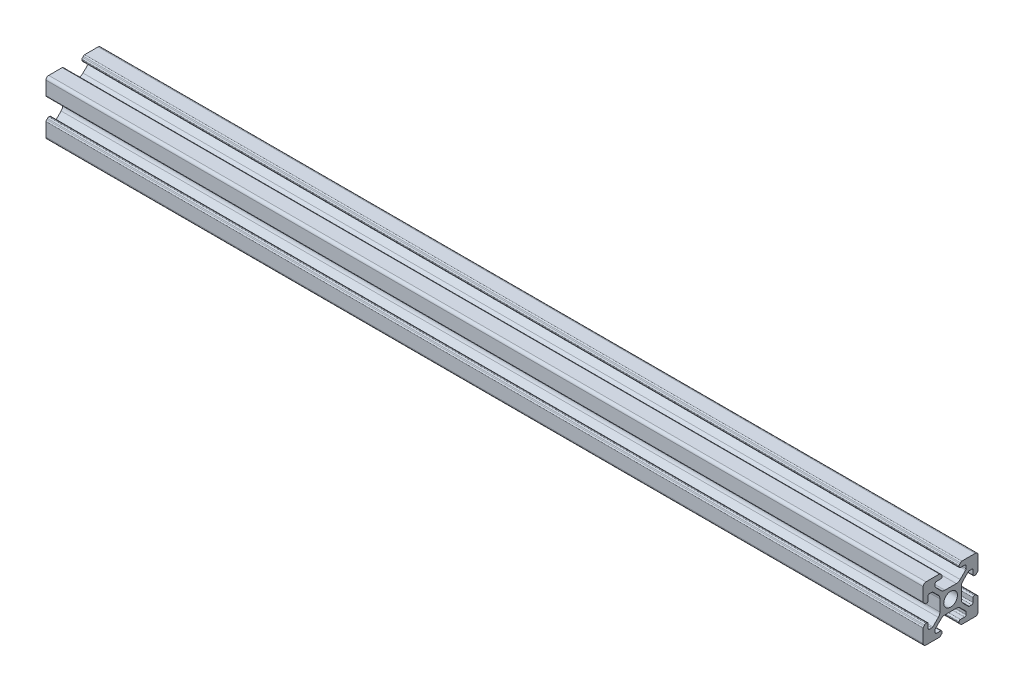
SolidWorks part; units mm, degrees
material "6061 Alloy"
ref_plane "Front Plane" through (0, 0, 0) normal (0, 0, 1) x (1, 0, 0)
ref_plane "Top Plane" through (0, 0, 0) normal (0, 1, 0) x (1, 0, 0)
ref_plane "Right Plane" through (0, 0, 0) normal (1, 0, 0) x (0, 0, -1)
sketch "Sketch1" plane through (0, 0, 0) normal (1, 0, 0) x (0, 0, -1)
  line L0 (10, 10) -> (-10, -10) construction
  line L1 (-10, 10) -> (10, 10)
  line L2 (-10, 10) -> (-10, -10)
  line L3 (-10, -10) -> (10, -10)
  line L4 (10, 10) -> (10, -10)
  dimension "D1" = 20
extrude "Boss-Extrude1" add sketch "Sketch1" along normal blind 320
fillet "Fillet1" radius 1 4 edges at (160, -10, -10) (160, -10, 10) (160, 10, -10) (160, 10, 10)
sketch "Sketch3" plane through (0, 0, 0) normal (-1, 0, 0) x (0, 0, 1)
  line L0 (-3.6, 10) -> (3.6, 10)
  line L1 (-9, 10) -> (9, 10) construction
  line L2 (3.6, 10) -> (3.6, 9.5)
  line L3 (3.6, 9.5) -> (3.1, 9.5)
  line L4 (3.1, 9.5) -> (3.1, 8.2)
  line L5 (3.1, 8.2) -> (5.63, 8.2)
  line L6 (5.63, 8.2) -> (5.63, 6.6199)
  line L7 (5.63, 6.6199) -> (2.9101, 3.9)
  line L8 (2.9101, 3.9) -> (-2.9101, 3.9)
  line L9 (-2.9101, 3.9) -> (-5.63, 6.6199)
  line L10 (-5.63, 6.6199) -> (-5.63, 8.2)
  line L11 (-5.63, 8.2) -> (-3.1, 8.2)
  line L12 (-3.1, 8.2) -> (-3.1, 9.5)
  line L13 (-3.1, 9.5) -> (-3.6, 9.5)
  line L14 (-3.6, 9.5) -> (-3.6, 10)
  line L15 (0, 10) -> (0, 3.9) construction
  line L16 (10, 3.6) -> (10, -3.6)
  line L17 (10, -3.6) -> (9.5, -3.6)
  line L18 (9.5, -3.6) -> (9.5, -3.1)
  line L19 (9.5, -3.1) -> (8.2, -3.1)
  line L20 (8.2, -3.1) -> (8.2, -5.63)
  line L21 (8.2, -5.63) -> (6.6199, -5.63)
  line L22 (6.6199, -5.63) -> (3.9, -2.9101)
  line L23 (3.9, -2.9101) -> (3.9, 2.9101)
  line L24 (3.9, 2.9101) -> (6.6199, 5.63)
  line L25 (6.6199, 5.63) -> (8.2, 5.63)
  line L26 (8.2, 5.63) -> (8.2, 3.1)
  line L27 (8.2, 3.1) -> (9.5, 3.1)
  line L28 (9.5, 3.1) -> (9.5, 3.6)
  line L29 (9.5, 3.6) -> (10, 3.6)
  line L30 (10, 0) -> (3.9, 0) construction
  line L31 (3.6, -10) -> (-3.6, -10)
  line L32 (-3.6, -10) -> (-3.6, -9.5)
  line L33 (-3.6, -9.5) -> (-3.1, -9.5)
  line L34 (-3.1, -9.5) -> (-3.1, -8.2)
  line L35 (-3.1, -8.2) -> (-5.63, -8.2)
  line L36 (-5.63, -8.2) -> (-5.63, -6.6199)
  line L37 (-5.63, -6.6199) -> (-2.9101, -3.9)
  line L38 (-2.9101, -3.9) -> (2.9101, -3.9)
  line L39 (2.9101, -3.9) -> (5.63, -6.6199)
  line L40 (5.63, -6.6199) -> (5.63, -8.2)
  line L41 (5.63, -8.2) -> (3.1, -8.2)
  line L42 (3.1, -8.2) -> (3.1, -9.5)
  line L43 (3.1, -9.5) -> (3.6, -9.5)
  line L44 (3.6, -9.5) -> (3.6, -10)
  line L45 (0, -10) -> (0, -3.9) construction
  line L46 (-10, -3.6) -> (-10, 3.6)
  line L47 (-10, 3.6) -> (-9.5, 3.6)
  line L48 (-9.5, 3.6) -> (-9.5, 3.1)
  line L49 (-9.5, 3.1) -> (-8.2, 3.1)
  line L50 (-8.2, 3.1) -> (-8.2, 5.63)
  line L51 (-8.2, 5.63) -> (-6.6199, 5.63)
  line L52 (-6.6199, 5.63) -> (-3.9, 2.9101)
  line L53 (-3.9, 2.9101) -> (-3.9, -2.9101)
  line L54 (-3.9, -2.9101) -> (-6.6199, -5.63)
  line L55 (-6.6199, -5.63) -> (-8.2, -5.63)
  line L56 (-8.2, -5.63) -> (-8.2, -3.1)
  line L57 (-8.2, -3.1) -> (-9.5, -3.1)
  line L58 (-9.5, -3.1) -> (-9.5, -3.6)
  line L59 (-9.5, -3.6) -> (-10, -3.6)
  line L60 (-10, 0) -> (-3.9, 0) construction
  line L61 (10, 9) -> (10, -9) construction
  line L62 (-10, -9) -> (-10, 9) construction
  point P4 (0, 10)
  point P17 (0, 0)
  point P26 (10, 0)
  point P43 (0, -10)
  point P60 (-10, 0)
  point P75 (0, 0)
  dimension "D1" = 135
  dimension "D2" = 6.2
  dimension "D3" = 7.2
  dimension "D4" = 6.1
  dimension "D5" = 11.26
  dimension "D6" = 0.5
  dimension "D8" = 1.4
  dimension "D9" = 1.8
  dimension "D7" = 4
extrude "Cut-Extrude1" cut sketch "Sketch3" against normal through all
hole_wizard "Ø5.0 (5) Diameter Hole1" positions "Sketch4" profile "Sketch5" hole size "Ø5.0" standard "ANSI Metric" end condition through all
sketch "Sketch4" plane through (0, 0, 0) normal (-1, 0, 0) x (0, 0, 1)
  point P0 (0, 0)
sketch "Sketch5" plane through (0, 0, 0) normal (0, 1, 0) x (0, 0, 1)
  line L0 (0, 0) -> (0, 320)
  line L1 (0, 320) -> (2.5, 320)
  line L2 (2.5, 320) -> (2.5, 0)
  line L5 (2.5, 0) -> (0, 0)
  line L11 (0, -6.35) -> (0, 107.95) construction
  dimension "Thru Hole Dia." = 5
  dimension "Thru Hole Depth" = 320
fillet "Fillet2" radius 2 8 edges at (160, -3.9, -2.9101) (160, -3.9, 2.9101) (160, -2.9101, 3.9) (160, 2.9101, 3.9) (160, 3.9, 2.9101) (160, 3.9, -2.9101) (160, 2.9101, -3.9) (160, -2.9101, -3.9)
fillet "Fillet3" radius 0.5 20 edges at (160, 3.6, -10) (160, 3.1, -9.5) (160, 3.1, -8.2) (160, 5.63, -8.2) (160, 5.63, -6.6199) (160, 3.6, 10) (160, 3.1, 9.5) (160, 3.1, 8.2) (160, 5.63, 8.2) (160, 5.63, 6.6199) (160, 6.6199, 5.63) (160, 8.2, 5.63) (160, 8.2, 3.1) (160, 9.5, 3.1) (160, 10, 3.6) (160, 9.5, -3.1) (160, 10, -3.6) (160, 8.2, -3.1) (160, 8.2, -5.63) (160, 6.6199, -5.63)
fillet "Fillet4" radius 0.5 20 edges at (160, -3.6, 10) (160, -3.1, 9.5) (160, -3.1, 8.2) (160, -5.63, 8.2) (160, -5.63, 6.6199) (160, -6.6199, 5.63) (160, -8.2, 5.63) (160, -8.2, 3.1) (160, -10, 3.6) (160, -9.5, 3.1) (160, -10, -3.6) (160, -9.5, -3.1) (160, -8.2, -3.1) (160, -8.2, -5.63) (160, -6.6199, -5.63) (160, -5.63, -6.6199) (160, -5.63, -8.2) (160, -3.1, -8.2) (160, -3.1, -9.5) (160, -3.6, -10)
fillet "Fillet5" radius 0.5 8 edges at (160, 3.6, -9.5) (160, -3.6, -9.5) (160, -9.5, -3.6) (160, -9.5, 3.6) (160, -3.6, 9.5) (160, 3.6, 9.5) (160, 9.5, 3.6) (160, 9.5, -3.6)
